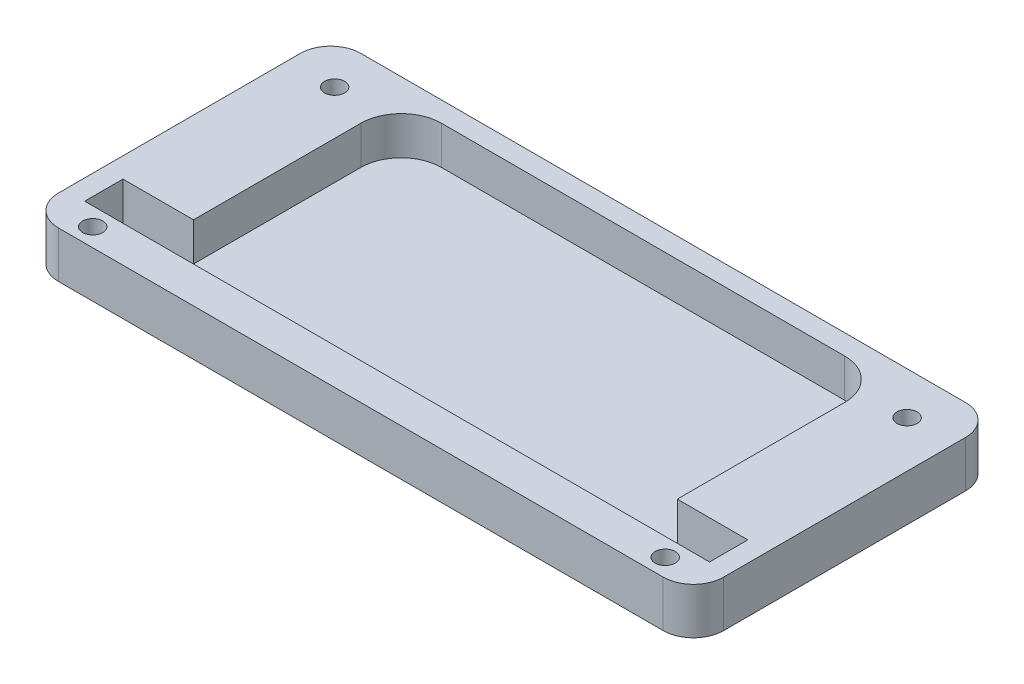
SolidWorks part; units mm, degrees
ref_plane "Спереди" through (0, 0, 0) normal (0, 0, 1) x (1, 0, 0)
ref_plane "Сверху" through (0, 0, 0) normal (0, 1, 0) x (1, 0, 0)
ref_plane "Справа" through (0, 0, 0) normal (1, 0, 0) x (0, 0, -1)
sketch "Эскиз1" plane through (0, 0, 0) normal (0, 1, 0) x (1, 0, 0)
  line L0 (0, 0) -> (0, 30931.8439) construction
  line L1 (0, 0) -> (-30931.8439, 0) construction
  line L2 (77.5, -4.75) -> (-77.5, -4.75)
  line L3 (-77.5, -4.75) -> (-77.5, 4.75)
  line L4 (-77.5, 4.75) -> (-60, 4.75)
  line L5 (-60, 4.75) -> (-60, 56.25)
  line L6 (-60, 56.25) -> (60, 56.25)
  line L7 (60, 4.75) -> (60, 56.25)
  line L8 (77.5, 4.75) -> (60, 4.75)
  line L9 (77.5, -4.75) -> (77.5, 4.75)
  line L10 (-82.5, -13.75) -> (82.5, -13.75)
  line L11 (-82.5, -13.75) -> (-82.5, 61.25)
  line L12 (-82.5, 61.25) -> (82.5, 61.25)
  line L13 (82.5, -13.75) -> (82.5, 61.25)
  line L14 (-71, -4.75) -> (-71, -13.75) construction
  circle A0 centre (-71, -9.25) radius 2.5
  circle A1 centre (-71, 50.75) radius 2.5
  circle A2 centre (71, -9.25) radius 2.5
  circle A3 centre (71, 50.75) radius 2.5
  point P28 (-71, -9.25)
  dimension "D7" = 5
  dimension "D9" = 142
  dimension "D1" = 155
  dimension "D2" = 9.5
  dimension "D3" = 61
  dimension "D4" = 120
  dimension "D5" = 5
  dimension "D6" = 5
  dimension "D8" = 9
  dimension "D10" = 60
extrude "Бобышка-Вытянуть1" add sketch "Эскиз1" along normal blind 9.5
extrude "Бобышка-Вытянуть2" add sketch "Эскиз1<2>" against normal blind 2 contours L10 L13 L12 L11 A2 A1 A0 L9 L2 L3 L4 L5 L6 L7 L8 A3 | L2 L9 L8 L7 L6 L5 L4 L3 region at (0, 0, -24.6312) region at (-80.6875, 0, -23.75)
sketch "Эскиз1<2>" plane through (0, 0, 0) normal (0, 1, 0) x (1, 0, 0) same geometry as "Эскиз1"
fillet "Скругление1" radius 10 2 edges at (60, 4.75, -56.25) (-60, 4.75, -56.25)
fillet "Скругление2" radius 7.5 4 edges at (82.5, 3.75, 13.75) (82.5, 3.75, -61.25) (-82.5, 3.75, -61.25) (-82.5, 3.75, 13.75)
